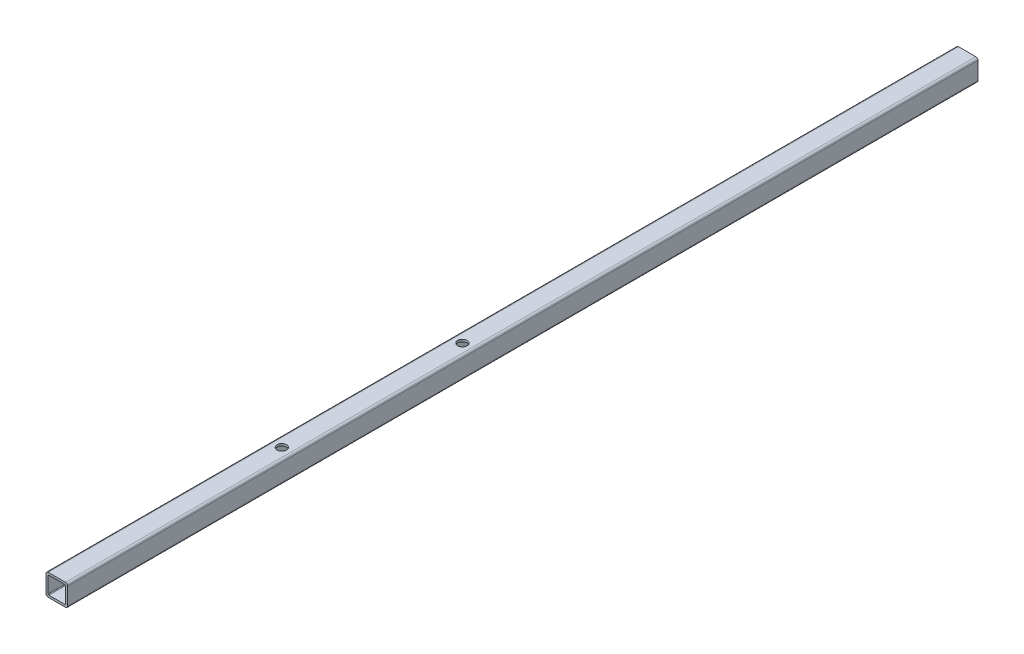
SolidWorks part; units mm, degrees
material "1.0553 (S355J0)"
ref_plane "Płaszczyzna przednia" through (0, 0, 0) normal (0, 0, 1) x (1, 0, 0)
ref_plane "Płaszczyzna górna" through (0, 0, 0) normal (0, 1, 0) x (1, 0, 0)
ref_plane "Płaszczyzna prawa" through (0, 0, 0) normal (1, 0, 0) x (0, 0, -1)
sketch "Szkic1" plane through (0, 0, 0) normal (0, 0, 1) x (1, 0, 0)
  line L0 (0, -55) -> (0, 55) construction
  line L1 (-12, -15) -> (12, -15)
  line L2 (-15, -12) -> (-15, 12)
  line L3 (-12, 15) -> (12, 15)
  line L4 (15, -12) -> (15, 12)
  line L5 (-11, -12) -> (11, -12)
  line L6 (-12, -11) -> (-12, 11)
  line L7 (-11, 12) -> (11, 12)
  line L8 (12, -11) -> (12, 11)
  line L10 (55, 0) -> (-55, 0) construction
  arc A0 (-12, -15) -> (-15, -12) centre (-12, -12) cw
  arc A1 (-15, 12) -> (-12, 15) centre (-12, 12) cw
  arc A2 (12, 15) -> (15, 12) centre (12, 12) cw
  arc A3 (15, -12) -> (12, -15) centre (12, -12) cw
  arc A4 (-12, -11) -> (-11, -12) centre (-11, -11) ccw
  arc A5 (11, -12) -> (12, -11) centre (11, -11) ccw
  arc A6 (12, 11) -> (11, 12) centre (11, 11) ccw
  arc A7 (-11, 12) -> (-12, 11) centre (-11, 11) ccw
  point P11 (0, 0)
  point P28 (0, -15)
  point P31 (-15, 0)
  dimension "D7" = 3
  dimension "D8" = 1
  dimension "D1" = 30
  dimension "D2" = 30
  dimension "D3" = 3
  dimension "D4" = 3
  dimension "D5" = 3
  dimension "D6" = 3
extrude "Dodanie-wyciągnięcie1" add sketch "Szkic1" along normal blind 1260
sketch "Szkic4" [suppressed] plane through (0, 0, 0) normal (1, 0, 0) x (0, 0, -1)
  line L0 (-119.2, 0) -> (0, 0) construction
  line L1 (-119.2, -12) -> (-119.2, 12) construction
  circle A0 centre (-59.6, 0) radius 5
  dimension "D1" = 10
extrude "Wytnij-wyciągnięcie3" [suppressed] cut sketch "Szkic4" along normal blind 29 and the other way blind 45
sketch "Szkic2" [suppressed] plane through (0, 0, 0) normal (1, 0, 0) x (0, 0, -1)
  line L4 (-1260, -15) -> (0, -15) construction
  line L6 (-1260, 15) -> (-1260, -15)
  line L7 (-1260, -15) -> (-420, -15)
  line L9 (-420, -15) -> (-402.6795, 15)
  line L10 (-1260, 15) -> (0, 15) construction
  line L11 (-402.6795, 15) -> (-1260, 15)
  line L12 (-17.3205, -15) -> (0, 15)
  line L14 (0, 15) -> (0, -15)
  line L15 (0, -15) -> (-17.3205, -15)
  dimension "D1" = 60
  dimension "D2" = 420
extrude "Wytnij-wyciągnięcie1" [suppressed] cut sketch "Szkic2" against normal blind 72 and the other way blind 88
sketch "Szkic3" [suppressed] plane through (0, 0, 0) normal (1, 0, 0) x (0, 0, -1)
  line L0 (-320, 15) -> (-320, -15) construction
  line L1 (-640, 15) -> (0, 15) construction
  line L2 (-640, -15) -> (0, -15) construction
  line L3 (-640, 0) -> (0, 0) construction
  line L4 (-640, -12) -> (-640, 12) construction
  circle A0 centre (-390, 0) radius 5
  circle A1 centre (-250, 0) radius 5
  dimension "D2" = 10
  dimension "D1" = 140
extrude "Wytnij-wyciągnięcie2" [suppressed] cut sketch "Szkic3" along normal blind 42 and the other way blind 37
sketch "Szkic5" [suppressed] plane through (-15, 0, 0) normal (-1, 0, 0) x (0, 0, 1)
  line L1 (185, 12) -> (185, -12) construction
  circle A0 centre (20, 0) radius 6.25
  circle A1 centre (140, 0) radius 6.25
  dimension "D3" = 12.5
  dimension "D1" = 120
  dimension "D4" = 45
extrude "Wytnij-wyciągnięcie4" [suppressed] cut sketch "Szkic5" against normal up to surface (30 mm away) up to face at (15, 0, 630)
sketch "Szkic6" plane through (0, 15, 0) normal (0, 1, 0) x (1, 0, 0)
  line L0 (12, -1260) -> (-12, -1260) construction
  line L1 (0, -16.5) -> (0, 16.5) construction
  circle A0 centre (0, -948.6) radius 6.5
  circle A1 centre (0, -698.6) radius 6.5
  point P6 (0, 0)
  point P7 (0, 0)
  point P10 (0, 0)
  dimension "D3" = 13
  dimension "D1" = 311.4
  dimension "D2" = 250
extrude "Wytnij-wyciągnięcie5" cut sketch "Szkic6" against normal up to surface (30 mm away) up to face at (0, -15, 630)
